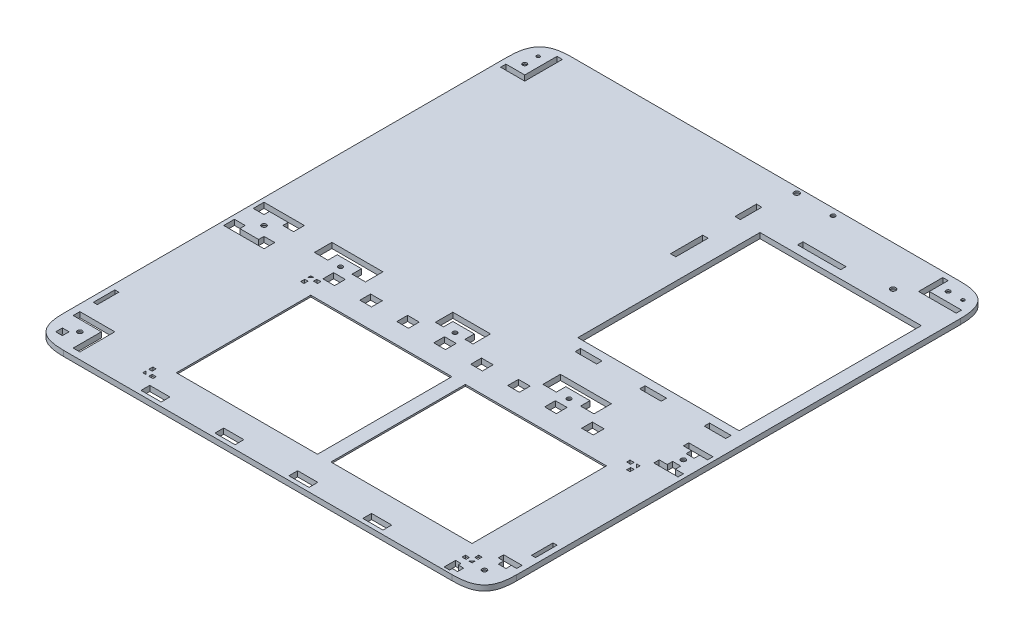
SolidWorks part; units mm, degrees
ref_plane "Front Plane" through (0, 0, 0) normal (0, 0, 1) x (1, 0, 0)
ref_plane "Top Plane" through (0, 0, 0) normal (0, 1, 0) x (1, 0, 0)
ref_plane "Right Plane" through (0, 0, 0) normal (1, 0, 0) x (0, 0, -1)
sketch "Sketch1" plane through (0, 0, 0) normal (0, 1, 0) x (1, 0, 0)
  line L1 (0, 0) -> (337, 0)
  line L2 (0, 0) -> (0, 377.97)
  line L3 (0, 377.97) -> (337, 377.97)
  line L4 (337, 0) -> (337, 377.97)
  line L5 (70.28, 137.5) -> (310.28, 137.5)
  line L6 (70.28, 137.5) -> (70.28, 17.5)
  line L7 (70.28, 17.5) -> (310.28, 17.5)
  line L8 (310.28, 137.5) -> (310.28, 17.5)
  dimension "D1" = 337
  dimension "D2" = 377.97
  dimension "D3" = 240
  dimension "D4" = 120
  dimension "D5" = 17.5
  dimension "D6" = 26.72
extrude "Boss-Extrude1" add sketch "Sketch1" against normal blind 4
fillet "Fillet1" radius 24 4 edges at (0, -2, 0) (337, -2, 0) (0, -2, -377.97) (337, -2, -377.97) conic rho 0.55
sketch "Sketch3" plane through (0, 0, 0) normal (0, 1, 0) x (1, 0, 0)
  line L0 (337, 24) -> (337, 353.97) construction
  line L1 (24, 0) -> (313, 0) construction
  line L2 (0, 353.97) -> (0, 24) construction
  line L3 (309, 4) -> (309, 2)
  line L4 (305, 10.5) -> (309, 10.5)
  line L5 (305, 10.5) -> (305, 2)
  line L6 (305, 2) -> (309, 2)
  line L7 (309, 10.5) -> (309, 8.5)
  line L8 (309, 8.5) -> (313, 8.5)
  line L10 (309, 4) -> (313, 4)
  line L11 (313, 8.5) -> (313, 4)
  line L12 (329, 28) -> (333, 28)
  line L13 (319.28, 32) -> (333, 32)
  line L14 (319.28, 32) -> (319.28, 28)
  line L15 (319.28, 28) -> (323.28, 28)
  line L16 (333, 32) -> (333, 28)
  line L18 (323.28, 28) -> (323.28, 24)
  line L19 (323.28, 24) -> (329, 24)
  line L20 (329, 28) -> (329, 24)
  line L21 (328, 151) -> (334, 151)
  line L30 (26, 5) -> (31, 5)
  line L36 (26, 5) -> (26, 26)
  line L37 (9, 14) -> (14, 14)
  line L38 (9, 14) -> (9, 9)
  line L39 (9, 9) -> (14, 9)
  line L40 (14, 14) -> (14, 9)
  line L41 (26, 31) -> (31, 31)
  line L42 (31, 5) -> (31, 31)
  line L43 (26, 31) -> (5, 31)
  line L45 (26, 26) -> (5, 26)
  line L46 (5, 31) -> (5, 26)
  line L47 (3, 140) -> (33, 140)
  line L48 (3, 140) -> (3, 144)
  line L49 (11, 144) -> (25, 144)
  line L50 (33, 140) -> (33, 144)
  line L52 (3, 144) -> (3, 148)
  line L53 (3, 148) -> (11, 148)
  line L54 (11, 144) -> (11, 148)
  line L56 (33, 144) -> (33, 148)
  line L57 (33, 148) -> (25, 148)
  line L58 (25, 144) -> (25, 148)
  line L59 (3, 170) -> (33, 170)
  line L60 (3, 170) -> (3, 166)
  line L61 (11, 166) -> (25, 166)
  line L62 (33, 170) -> (33, 166)
  line L64 (3, 166) -> (3, 162)
  line L65 (3, 162) -> (11, 162)
  line L66 (11, 166) -> (11, 162)
  line L68 (33, 166) -> (33, 162)
  line L69 (33, 162) -> (25, 162)
  line L70 (25, 166) -> (25, 162)
  line L71 (316, 147) -> (334, 147)
  line L72 (316, 147) -> (316, 151)
  line L73 (316, 151) -> (322, 151)
  line L74 (334, 147) -> (334, 151)
  line L76 (322, 151) -> (322, 155)
  line L77 (322, 155) -> (328, 155)
  line L78 (328, 151) -> (328, 155)
  line L79 (328, 169) -> (334, 169)
  line L80 (316, 173) -> (334, 173)
  line L81 (316, 173) -> (316, 169)
  line L82 (316, 169) -> (322, 169)
  line L83 (334, 173) -> (334, 169)
  line L85 (322, 169) -> (322, 165)
  line L86 (322, 165) -> (328, 165)
  line L87 (328, 169) -> (328, 165)
  line L88 (313, 377.97) -> (24, 377.97) construction
  line L89 (333, 42) -> (330, 42)
  line L90 (333, 42) -> (333, 58)
  line L91 (333, 58) -> (330, 58)
  line L92 (330, 42) -> (330, 58)
  line L93 (4, 42) -> (7, 42)
  line L94 (4, 42) -> (4, 58)
  line L95 (4, 58) -> (7, 58)
  line L96 (7, 42) -> (7, 58)
  line L97 (187.4, 351.97) -> (191.4, 351.97)
  line L98 (187.4, 351.97) -> (187.4, 335.97)
  line L99 (187.4, 335.97) -> (191.4, 335.97)
  line L100 (191.4, 351.97) -> (191.4, 335.97)
  line L102 (187.4, 311.97) -> (191.4, 311.97)
  line L103 (187.4, 311.97) -> (187.4, 287.97)
  line L104 (187.4, 287.97) -> (191.4, 287.97)
  line L105 (191.4, 311.97) -> (191.4, 287.97)
  line L106 (207, 334.97) -> (327, 334.97)
  line L107 (207, 334.97) -> (207, 199.47)
  line L108 (207, 199.47) -> (327, 199.47)
  line L109 (327, 334.97) -> (327, 199.47)
  line L110 (327, 193.47) -> (311, 193.47)
  line L111 (327, 193.47) -> (327, 189.47)
  line L112 (327, 189.47) -> (311, 189.47)
  line L113 (311, 193.47) -> (311, 189.47)
  line L114 (279, 193.47) -> (263, 193.47)
  line L115 (279, 193.47) -> (279, 189.47)
  line L116 (279, 189.47) -> (263, 189.47)
  line L117 (263, 193.47) -> (263, 189.47)
  line L118 (231, 193.47) -> (215, 193.47)
  line L119 (231, 193.47) -> (231, 189.47)
  line L120 (231, 189.47) -> (215, 189.47)
  line L121 (215, 193.47) -> (215, 189.47)
  line L122 (229, 344.97) -> (261, 344.97)
  line L123 (229, 344.97) -> (229, 340.97)
  line L124 (229, 340.97) -> (261, 340.97)
  line L125 (261, 344.97) -> (261, 340.97)
  line L126 (332, 355.97) -> (304, 355.97)
  line L127 (332, 355.97) -> (332, 359.97)
  line L128 (332, 359.97) -> (308, 359.97)
  line L129 (304, 355.97) -> (304, 359.97)
  line L131 (304, 359.97) -> (304, 373.97)
  line L132 (304, 373.97) -> (308, 373.97)
  line L133 (308, 359.97) -> (308, 373.97)
  line L134 (18, 372.97) -> (22, 372.97)
  line L135 (18, 372.97) -> (18, 348.97)
  line L136 (18, 344.97) -> (22, 344.97)
  line L137 (22, 372.97) -> (22, 344.97)
  line L138 (18, 344.97) -> (4, 344.97)
  line L140 (18, 348.97) -> (4, 348.97)
  line L141 (4, 344.97) -> (4, 348.97)
  circle A0 centre (322, 15) radius 1.75
  circle A1 centre (18, 18) radius 1.75
  circle A2 centre (18, 155) radius 1.75
  circle A3 centre (325, 160) radius 1.75
  circle A4 centre (195.4, 373.97) radius 2
  circle A5 centre (293, 347.97) radius 2
  circle A6 centre (315, 366.97) radius 1.6
  circle A7 centre (326, 366.97) radius 1.2
  circle A8 centre (11, 355.97) radius 1.6
  circle A9 centre (11, 365.97) radius 1.2
  circle A10 centre (223.4, 372.97) radius 1.6
  point P37 (5, 28.5)
  point P127 (306, 373.97)
  dimension "D3" = 3.5
  dimension "D6" = 3.5
  dimension "D45" = 3.5
  dimension "D62" = 3.5
  dimension "D79" = 4
  dimension "D80" = 4
  dimension "D81" = 4
  dimension "D100" = 4
  dimension "D101" = 44
  dimension "D109" = 3.2
  dimension "D110" = 7
  dimension "D111" = 7
  dimension "D112" = 2.4
  dimension "D113" = 7
  dimension "D114" = 11
  dimension "D122" = 3.2
  dimension "D123" = 7
  dimension "D124" = 7
  dimension "D125" = 2.4
  dimension "D126" = 10
  dimension "D127" = 7
  dimension "D128" = 5
  dimension "D129" = 3.2
  dimension "D130" = 113.6
  dimension "D1" = 15
  dimension "D2" = 15
  dimension "D4" = 18
  dimension "D5" = 18
  dimension "D7" = 24
  dimension "D8" = 4
  dimension "D9" = 2
  dimension "D10" = 2
  dimension "D11" = 4.5
  dimension "D12" = 2
  dimension "D13" = 4
  dimension "D14" = 4
  dimension "D15" = 13.72
  dimension "D16" = 4
  dimension "D17" = 4
  dimension "D18" = 4
  dimension "D19" = 4
  dimension "D20" = 24
  dimension "D21" = 5
  dimension "D22" = 5
  dimension "D23" = 9
  dimension "D24" = 9
  dimension "D25" = 26
  dimension "D26" = 5
  dimension "D27" = 5
  dimension "D28" = 5
  dimension "D29" = 21
  dimension "D30" = 5
  dimension "D31" = 30
  dimension "D32" = 4
  dimension "D33" = 4
  dimension "D34" = 8
  dimension "D35" = 8
  dimension "D36" = 4
  dimension "D37" = 30
  dimension "D38" = 4
  dimension "D39" = 4
  dimension "D40" = 4
  dimension "D41" = 30
  dimension "D42" = 140
  dimension "D43" = 3
  dimension "D44" = 3
  dimension "D46" = 11
  dimension "D47" = 4
  dimension "D48" = 4
  dimension "D49" = 4
  dimension "D50" = 18
  dimension "D51" = 3
  dimension "D52" = 6
  dimension "D53" = 6
  dimension "D54" = 4
  dimension "D55" = 4
  dimension "D56" = 4
  dimension "D57" = 18
  dimension "D58" = 6
  dimension "D59" = 6
  dimension "D60" = 10
  dimension "D61" = 147
  dimension "D63" = 5
  dimension "D64" = 9
  dimension "D65" = 3
  dimension "D66" = 16
  dimension "D67" = 10
  dimension "D68" = 4
  dimension "D69" = 4
  dimension "D70" = 16
  dimension "D71" = 3
  dimension "D72" = 0
  dimension "D73" = 145.6
  dimension "D74" = 26
  dimension "D75" = 4
  dimension "D76" = 16
  dimension "D77" = 24
  dimension "D78" = 24
  dimension "D82" = 43
  dimension "D83" = 10
  dimension "D84" = 135.5
  dimension "D85" = 120
  dimension "D86" = 4
  dimension "D87" = 6
  dimension "D88" = 16
  dimension "D89" = 10
  dimension "D90" = 16
  dimension "D91" = 32
  dimension "D92" = 4
  dimension "D93" = 6
  dimension "D94" = 16
  dimension "D95" = 32
  dimension "D96" = 32
  dimension "D97" = 4
  dimension "D98" = 6
  dimension "D99" = 76
  dimension "D102" = 13
  dimension "D103" = 4
  dimension "D104" = 5
  dimension "D105" = 28
  dimension "D106" = 22
  dimension "D107" = 4
  dimension "D108" = 4
  dimension "D115" = 5
  dimension "D116" = 4
  dimension "D117" = 28
  dimension "D118" = 4
  dimension "D119" = 14
  dimension "D120" = 4
  dimension "D121" = 4
extrude "Cut-Extrude1" cut sketch "Sketch3" against normal up to next (4 mm away)
ref_plane "Plane3" through (190.28, 0, 0) normal (-1, 0, 0) x (0, 0, 1)
ref_plane "Plane6" through (0, 0, -77.5) normal (0, 0, 1) x (1, 0, 0)
sketch "Sketch5" plane through (0, 0, 0) normal (0, 1, 0) x (1, 0, 0)
  line L0 (310.28, 17.5) -> (310.28, 137.5) construction
  line L3 (310.28, 15) -> (312.78, 15)
  line L4 (312.78, 17.5) -> (312.78, 15)
  line L5 (310.28, 22.5) -> (312.78, 22.5)
  line L6 (310.28, 22.5) -> (310.28, 19.5)
  line L7 (310.28, 19.5) -> (312.78, 19.5)
  line L8 (312.78, 22.5) -> (312.78, 19.5)
  line L9 (70.28, 17.5) -> (310.28, 17.5) construction
  line L10 (305.28, 17.5) -> (308.28, 17.5)
  line L11 (305.28, 17.5) -> (305.28, 15)
  line L12 (305.28, 15) -> (308.28, 15)
  line L13 (308.28, 17.5) -> (308.28, 15)
  line L14 (310.28, 15) -> (312.78, 17.5)
  dimension "D1" = 2.5
  dimension "D2" = 2.5
  dimension "D4" = 3
  dimension "D6" = 3
extrude "Cut-Extrude2" cut sketch "Sketch5" against normal up to next
mirror "Mirror1" about plane through (0, 0, -77.5) normal (0, 0, 1) of "Cut-Extrude2" second plane through (190.28, 0, 0) second plane normal (-1, 0, 0)
sketch "Sketch6" plane through (0, -4, 0) normal (0, -1, 0) x (1, 0, 0)
  circle A0 centre (18, -155) radius 3.5
  circle A1 centre (18, -18) radius 3.5
  circle A2 centre (322, -15) radius 3.5
  circle A3 centre (325, -160) radius 3.5
  circle A4 centre (195.4, -373.97) radius 3.5
  circle A5 centre (293, -347.97) radius 3.5
  circle A6 centre (315, -366.97) radius 3.5
  circle A7 centre (326, -366.97) radius 3
  circle A8 centre (11, -355.97) radius 3.5
  circle A9 centre (11, -365.97) radius 3
  circle A10 centre (223.4, -372.97) radius 3.5
  dimension "D1" = 7
  dimension "D2" = 7
  dimension "D3" = 7
  dimension "D4" = 7
  dimension "D5" = 7
  dimension "D6" = 7
  dimension "D7" = 6
  dimension "D8" = 7
  dimension "D9" = 7
  dimension "D10" = 6
  dimension "D11" = 7
extrude "Cut-Extrude3" cut sketch "Sketch6" against normal blind 2.8
sketch "Sketch7" plane through (0, 0, 0) normal (0, 1, 0) x (1, 0, 0)
  line L0 (310.28, 22.5) -> (310.28, 132.5) construction
  line L1 (275.48, 142.5) -> (266.78, 142.5)
  line L2 (275.48, 142.5) -> (275.48, 150.5)
  line L3 (275.48, 150.5) -> (266.78, 150.5)
  line L4 (266.78, 142.5) -> (266.78, 150.5)
  line L5 (305.28, 137.5) -> (75.28, 137.5) construction
  dimension "D1" = 34.8
  dimension "D2" = 5
  dimension "D3" = 8.7
  dimension "D4" = 8
extrude "Cut-Extrude4" cut sketch "Sketch7" against normal up to next
pattern_linear "LPattern1" count 8 spacing 27.5 along (-1, 0, 0) of "Cut-Extrude4"
sketch "Sketch8" plane through (0, 0, 0) normal (0, 1, 0) x (1, 0, 0)
  line L0 (275.48, 150.5) -> (266.78, 150.5) construction
  line L1 (262.1, 156.38) -> (252.1, 156.38)
  line L2 (262.1, 156.38) -> (262.1, 163.38)
  line L4 (252.1, 156.38) -> (252.1, 163.38)
  line L5 (266.78, 150.5) -> (266.78, 142.5) construction
  line L7 (252.1, 163.38) -> (234.1, 163.38)
  line L8 (262.1, 163.38) -> (262.1, 169.38)
  line L9 (262.1, 169.38) -> (224.1, 169.38)
  line L10 (224.1, 163.38) -> (224.1, 169.38)
  line L12 (224.1, 163.38) -> (224.1, 156.38)
  line L13 (224.1, 156.38) -> (234.1, 156.38)
  line L14 (234.1, 163.38) -> (234.1, 156.38)
  dimension "D1" = 5.88
  dimension "D2" = 4.68
  dimension "D3" = 10
  dimension "D4" = 7
  dimension "D5" = 38
  dimension "D6" = 6
  dimension "D7" = 7
  dimension "D8" = 10
extrude "Cut-Extrude5" cut sketch "Sketch8" against normal up to next
ref_plane "Plane7" through (158.1, 0, 0) normal (1, 0, 0) x (0, 0, -1)
sketch "Sketch9" plane through (0, 0, 0) normal (0, 1, 0) x (1, 0, 0)
  line L0 (252.1, 163.38) -> (252.1, 156.38) construction
  line L1 (234.1, 163.38) -> (252.1, 163.38) construction
  circle A0 centre (243.1, 156.88) radius 1.6
  dimension "D1" = 9
  dimension "D2" = 6.5
  dimension "D3" = 3.2
extrude "Cut-Extrude6" cut sketch "Sketch9" against normal up to next
sketch "Sketch10" plane through (0, -4, 0) normal (0, -1, 0) x (1, 0, 0)
  circle A0 centre (243.1, -156.88) radius 3.5
  dimension "D1" = 7
extrude "Cut-Extrude7" cut sketch "Sketch10" against normal blind 2.8
mirror "Mirror2" about plane through (158.1, 0, 0) normal (1, 0, 0) of "Cut-Extrude6", "Cut-Extrude7", "Cut-Extrude5"
sketch "Sketch11" plane through (0, 0, 0) normal (0, 1, 0) x (1, 0, 0)
  line L0 (224.1, 169.38) -> (224.1, 156.38) construction
  line L1 (172.1, 169.38) -> (144.1, 169.38)
  line L2 (172.1, 169.38) -> (172.1, 163.38)
  line L3 (166.1, 163.38) -> (150.1, 163.38)
  line L4 (144.1, 169.38) -> (144.1, 163.38)
  line L5 (262.1, 169.38) -> (224.1, 169.38) construction
  line L6 (158.1, -2.2) -> (158.1, 2.2) construction
  line L7 (224.1, 156.38) -> (234.1, 156.38) construction
  line L9 (172.1, 163.38) -> (172.1, 156.38)
  line L10 (172.1, 156.38) -> (166.1, 156.38)
  line L11 (166.1, 163.38) -> (166.1, 156.38)
  line L13 (144.1, 163.38) -> (144.1, 156.38)
  line L14 (144.1, 156.38) -> (150.1, 156.38)
  line L15 (150.1, 163.38) -> (150.1, 156.38)
  circle A0 centre (158.1, 156.88) radius 1.6
  dimension "D9" = 6.5
  dimension "D10" = 3.2
  dimension "D1" = 28
  dimension "D2" = 52
  dimension "D3" = 0
  dimension "D4" = 6
  dimension "D5" = 6
  dimension "D6" = 6
  dimension "D7" = 0
  dimension "D8" = 0
extrude "Cut-Extrude8" cut sketch "Sketch11" against normal up to next
sketch "Sketch12" plane through (0, -4, 0) normal (0, -1, 0) x (1, 0, 0)
  circle A0 centre (158.1, -156.88) radius 3.5
extrude "Cut-Extrude9" cut sketch "Sketch12" against normal blind 2.8
sketch "Sketch13" plane through (0, 0, 0) normal (0, 1, 0) x (1, 0, 0)
  line L0 (70.28, 132.5) -> (70.28, 22.5) construction
  line L1 (78.5, 9.5) -> (93.5, 9.5)
  line L2 (78.5, 9.5) -> (78.5, 3)
  line L3 (78.5, 3) -> (93.5, 3)
  line L4 (93.5, 9.5) -> (93.5, 3)
  line L6 (24, 0) -> (313, 0) construction
  dimension "D1" = 8.22
  dimension "D2" = 3
  dimension "D3" = 15
  dimension "D4" = 6.5
extrude "Cut-Extrude10" cut sketch "Sketch13" against normal blind 4
pattern_linear "LPattern2" count 4 spacing 55 along (1, 0, 0) of "Cut-Extrude10"
sketch "Sketch15" plane through (0, 0, 0) normal (0, 1, 0) x (1, 0, 0)
  line L0 (190.28, 1.1) -> (190.28, -1.1) construction
  line L1 (70.28, 137.5) -> (310.28, 137.5)
  line L2 (70.28, 137.5) -> (70.28, 17.5)
  line L3 (70.28, 17.5) -> (310.28, 17.5)
  line L4 (310.28, 137.5) -> (310.28, 17.5)
  line L5 (80.28, 127.5) -> (185.28, 127.5)
  line L6 (80.28, 127.5) -> (80.28, 27.5)
  line L7 (80.28, 27.5) -> (185.28, 27.5)
  line L8 (300.28, 127.5) -> (300.28, 27.5)
  line L10 (185.28, 127.5) -> (185.28, 27.5)
  line L12 (195.28, 127.5) -> (195.28, 27.5)
  line L13 (195.28, 127.5) -> (300.28, 127.5)
  line L14 (195.28, 27.5) -> (300.28, 27.5)
  dimension "D1" = 10
  dimension "D2" = 10
  dimension "D3" = 10
  dimension "D4" = 10
  dimension "D5" = 10
  dimension "D6" = 5
extrude "Boss-Extrude2" add sketch "Sketch15" against normal blind 1.2
